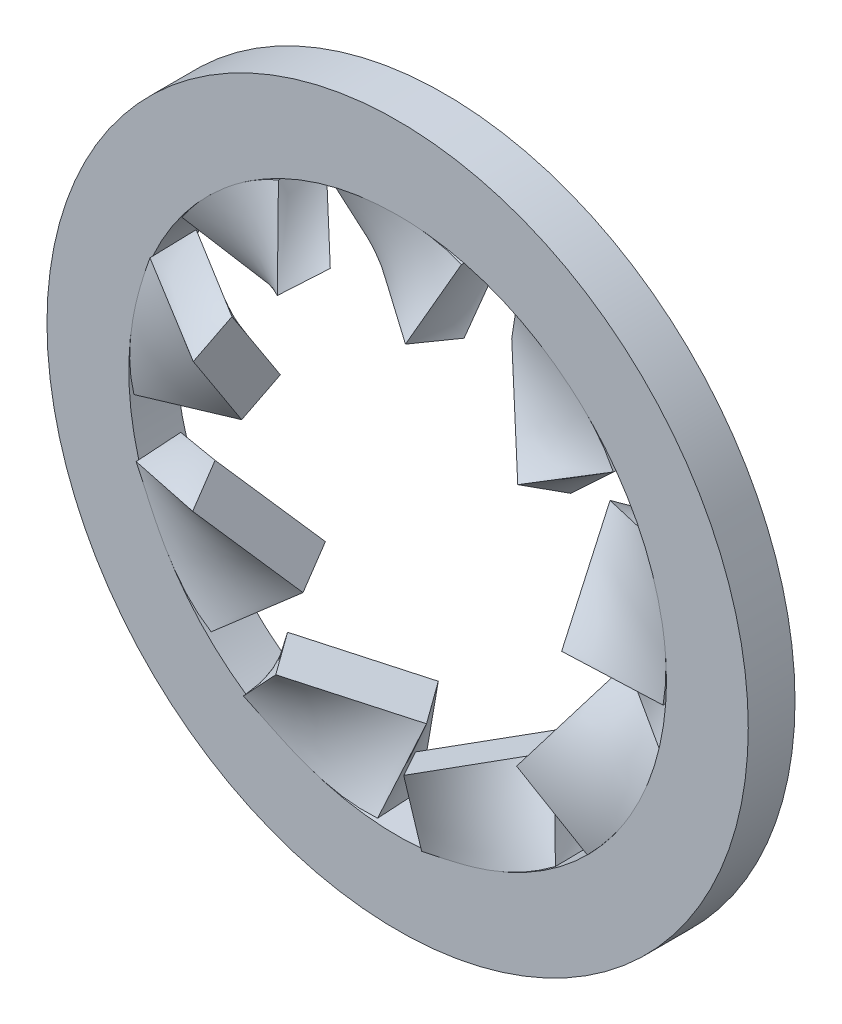
SolidWorks part; units mm, degrees
ref_plane "Front Plane" through (0, 0, 0) normal (0, 0, 1) x (1, 0, 0)
ref_plane "Top Plane" through (0, 0, 0) normal (0, 1, 0) x (1, 0, 0)
ref_plane "Right Plane" through (0, 0, 0) normal (1, 0, 0) x (0, 0, -1)
sketch "Sketch1" plane through (0, 0, 0) normal (0, 0, 1) x (1, 0, 0)
  line L0 (0, 1.6) -> (0, 3) construction
  circle A0 centre (0, 0) radius 1.6
  circle A1 centre (0, 0) radius 3
  circle A3 centre (0, 0) radius 2.3 construction
  point P6 (0, 2.3)
  point P7 (-1.6, 0)
  dimension "ID" = 3.2
  dimension "OD" = 6
ref_plane "Plane1" through (0, 1.6, 0) normal (0, 1, 0) x (-1, 0, 0)
ref_plane "Plane2" through (0, 2.3, 0) normal (0, 1, 0) x (-1, 0, 0)
sketch "Sketch2" plane through (0, 2.3, 0) normal (0, 1, 0) x (-1, 0, 0)
  line L0 (-0.6, 0) -> (0.6, 0) construction
  line L1 (-0.6, 0.2) -> (0.6, 0.2)
  line L2 (-0.6, 0.2) -> (-0.6, -0.2)
  line L3 (-0.6, -0.2) -> (0.6, -0.2)
  line L4 (0.6, 0.2) -> (0.6, -0.2)
  line L5 (0, 0) -> (0, 0.2) construction
  line L6 (2.3, 0) -> (-2.3, 0) construction
  dimension "D1" = 1.2
  dimension "thickness" = 0.4
sketch "Sketch3" plane through (0, 1.6, 0) normal (0, 1, 0) x (-1, 0, 0)
  line L0 (-0.2899, 0.4228) -> (-0.4964, 0.1279)
  line L1 (-0.2899, 0.4228) -> (0.4964, -0.1279)
  line L2 (-0.4964, 0.1279) -> (0.2899, -0.4228)
  line L3 (0.4964, -0.1279) -> (0.2899, -0.4228)
  line L4 (-0.3932, 0.2753) -> (0.3932, -0.2753) construction
  line L5 (0.1032, 0.1474) -> (-0.1032, -0.1474) construction
  line L7 (2.3, 0) -> (-2.3, 0) construction
  dimension "D1" = 0.96
  dimension "D2" = 0.36
  dimension "D3" = 35
loft "Loft1" add profiles "Sketch2", "Sketch3"
ref_axis "Axis1" through (0, 0, -0.5317) along (0, 0, 1)
pattern_circular "CirPattern1" count 9 over 360 about axis through (0, 0, -0.5317) along (0, 0, 1) of bodies 102
sketch "Sketch4" plane through (0, 0, 0) normal (0, 0, 1) x (1, 0, 0)
  circle A0 centre (0, 0) radius 2.3 construction
  circle A1 centre (0, 0) radius 2.3
extrude "Cut-Extrude1" cut sketch "Sketch4" against normal through all and the other way through all flip side to cut
sketch "Sketch5" plane through (0, 0, 0) normal (0, 0, 1) x (1, 0, 0)
  circle A0 centre (0, 0) radius 3 construction
  circle A1 centre (0, 0) radius 2.3 construction
  circle A2 centre (0, 0) radius 3
  circle A3 centre (0, 0) radius 2.3
extrude "Extrude1" add sketch "Sketch5" along normal mid plane 0.4
ref_axis "Axis2" through (0, 0, -0.4652) along (0, 0, 1)
equation "\"D1@Sketch2\" = \"thickness@Sketch2\" * 3"
equation "\"D1@Sketch3\" = \"D1@Sketch2\" * 0.8"
equation "\"D2@Sketch3\" = \"thickness@Sketch2\" * 0.9"
equation "\"D1@Extrude1\" = \"thickness@Sketch2\""
